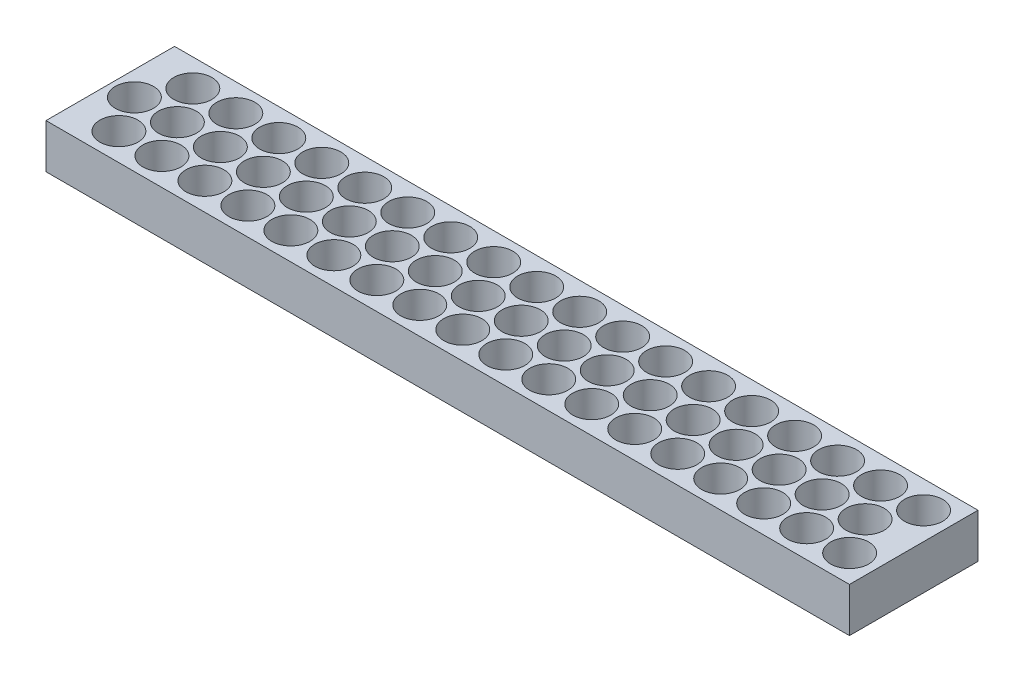
SolidWorks part; units mm, degrees
ref_plane "Front Plane" through (0, 0, 0) normal (0, 0, 1) x (1, 0, 0)
ref_plane "Top Plane" through (0, 0, 0) normal (0, 1, 0) x (1, 0, 0)
ref_plane "Right Plane" through (0, 0, 0) normal (1, 0, 0) x (0, 0, -1)
sketch "Sketch1" plane through (0, 0, 0) normal (0, 1, 0) x (1, 0, 0)
  line L0 (0, 0) -> (16.9862, 0) construction
  line L1 (38.4175, -50.8) -> (-38.4175, -50.8)
  line L2 (38.4175, -50.8) -> (38.4175, 50.8)
  line L3 (38.4175, 50.8) -> (-38.4175, 50.8)
  line L5 (38.4175, -50.8) -> (-38.4175, 50.8) construction
  line L6 (38.4175, 50.8) -> (-38.4175, -50.8) construction
  line L7 (16.9862, 0) -> (16.9862, 29.21) construction
  line L9 (-38.4175, 50.8) -> (-596.5825, 50.8)
  line L11 (-38.4175, -50.8) -> (-596.5825, -50.8)
  line L12 (-596.5825, 50.8) -> (-596.5825, -50.8)
  circle A0 centre (0, 0) radius 15.0813
  circle A1 centre (16.9862, 29.21) radius 15.0813
  circle A2 centre (16.9862, -29.21) radius 15.0813
  point P0 (0, 0)
  dimension "D3" = 30.1625
  dimension "D6" = 30.1625
  dimension "D1" = 101.6
  dimension "D2" = 21.4312
  dimension "D4" = 16.9862
  dimension "D5" = 29.21
  dimension "D7" = 635
extrude "Boss-Extrude1" add sketch "Sketch1" along normal blind 35.052 contours L9 L12 L11 L1 L2 L3 A0 A1 A2 | A1 | A0 | A2 region at (-289.0632, 0, 0)
extrude "Cut-Extrude3" cut sketch "Sketch1<3>" along normal through all both and the other way through all contours A0 | A0 | A1 | A2 region at (0, 0, 0)
sketch "Sketch1<3>" plane through (0, 0, 0) normal (0, 1, 0) x (1, 0, 0) same geometry as "Sketch1"
pattern_linear "LPattern1" count 18 spacing 33.9725 along (-1, 0, 0) of "Cut-Extrude3"
sketch "Sketch2" plane through (0, 35.052, 0) normal (0, 1, 0) x (1, 0, 0)
  line L0 (0, 0) -> (10.414, 0) construction
  line L1 (10.414, 0) -> (10.414, 50.8)
  line L2 (38.4175, 50.8) -> (-596.5825, 50.8) construction
  line L3 (10.414, 0) -> (10.414, -50.8)
  line L4 (38.4175, -50.8) -> (-596.5825, -50.8) construction
  line L6 (38.4175, -50.8) -> (38.4175, 50.8) construction
  point P11 (0, 0)
  dimension "D1" = 28.0035
ref_plane "Plane1" through (10.414, 0, 0) normal (1, 0, 0) x (0, 0, -1)
